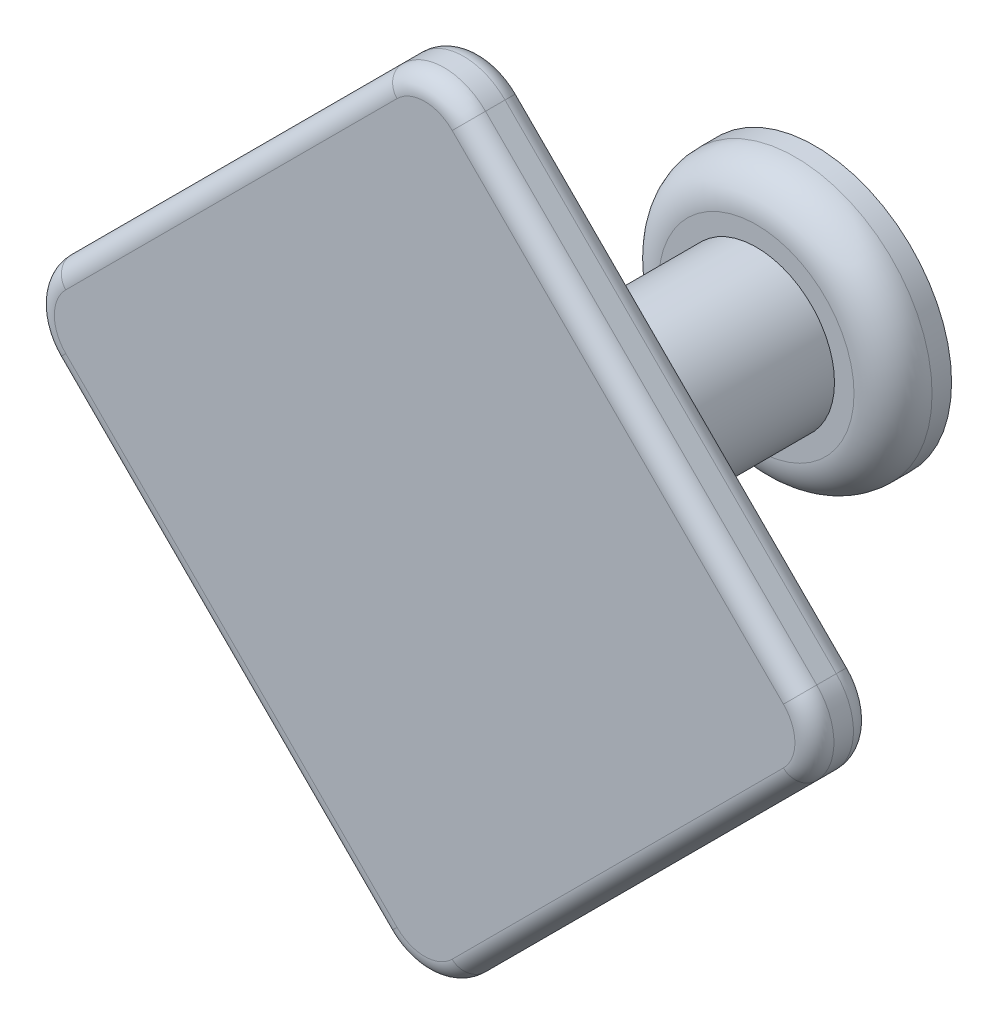
SolidWorks part; units mm, degrees
material "Brass"
ref_plane "Front Plane" through (0, 0, 0) normal (0, 0, 1) x (1, 0, 0)
ref_plane "Top Plane" through (0, 0, 0) normal (0, 1, 0) x (1, 0, 0)
ref_plane "Right Plane" through (0, 0, 0) normal (1, 0, 0) x (0, 0, -1)
sketch "Sketch1" plane through (0, 0, 0) normal (0, 0, 1) x (1, 0, 0)
  line L0 (-21.2132, 0) -> (0, 21.2132)
  line L1 (-21.2132, 0) -> (0, -21.2132)
  line L2 (0, 21.2132) -> (21.2132, 0)
  line L3 (0, -21.2132) -> (21.2132, 0)
  line L4 (-21.2132, 0) -> (21.2132, 0) construction
  line L5 (0, 21.2132) -> (0, -21.2132) construction
  circle A1 centre (0, 0) radius 2.5
  circle A2 centre (0, 0) radius 4
  circle A3 centre (0, 0) radius 7
  point P1 (0, 0)
  dimension "D2" = 5
  dimension "D1" = 30
  dimension "D3" = 1.5
  dimension "D4" = 3
extrude "Boss-Extrude1" add sketch "Sketch1" along normal mid plane 3 contours L1 L3 L2 L0 A2 | A2 A1 | A3 A2 | A1 region at (-10.1823, 10.1823, 0) region at (-3.8869, 0, 0) region at (-6.802, 0, 0)
fillet "Fillet1" radius 3 4 edges at (-21.2132, 0, 0) (21.2132, 0, 0) (0, -21.2132, 0) (0, 21.2132, 0)
fillet "Fillet3" radius 1 16 edges at (0, 19.9706, -1.5) (-10.6066, 10.6066, -1.5) (-19.9706, 0, -1.5) (-10.6066, -10.6066, -1.5) (0, -19.9706, -1.5) (10.6066, -10.6066, -1.5) (19.9706, 0, -1.5) (0, 19.9706, 1.5) (-10.6066, 10.6066, 1.5) (-19.9706, 0, 1.5) (-10.6066, -10.6066, 1.5) (0, -19.9706, 1.5) (10.6066, -10.6066, 1.5) (19.9706, 0, 1.5) (10.6066, 10.6066, -1.5) (10.6066, 10.6066, 1.5)
extrude "Boss-Extrude2" add sketch "Sketch1<3>" against normal blind 17 from surface contours A2 A1 region at (-3.8869, 0, 0) starting at face at (0, 0, -1.5)
sketch "Sketch1<3>" plane through (0, 0, 0) normal (0, 0, 1) x (1, 0, 0) same geometry as "Sketch1"
extrude "Boss-Extrude3" add sketch "Sketch1<4>" along normal blind 3 from surface contours A3 A2 region at (-6.802, 0, 0) starting at face at (2.5, 0, -18.5)
sketch "Sketch1<4>" plane through (0, 0, 0) normal (0, 0, 1) x (1, 0, 0) same geometry as "Sketch1"
fillet "Fillet4" radius 2 1 edges at (7, 0, -15.5)
